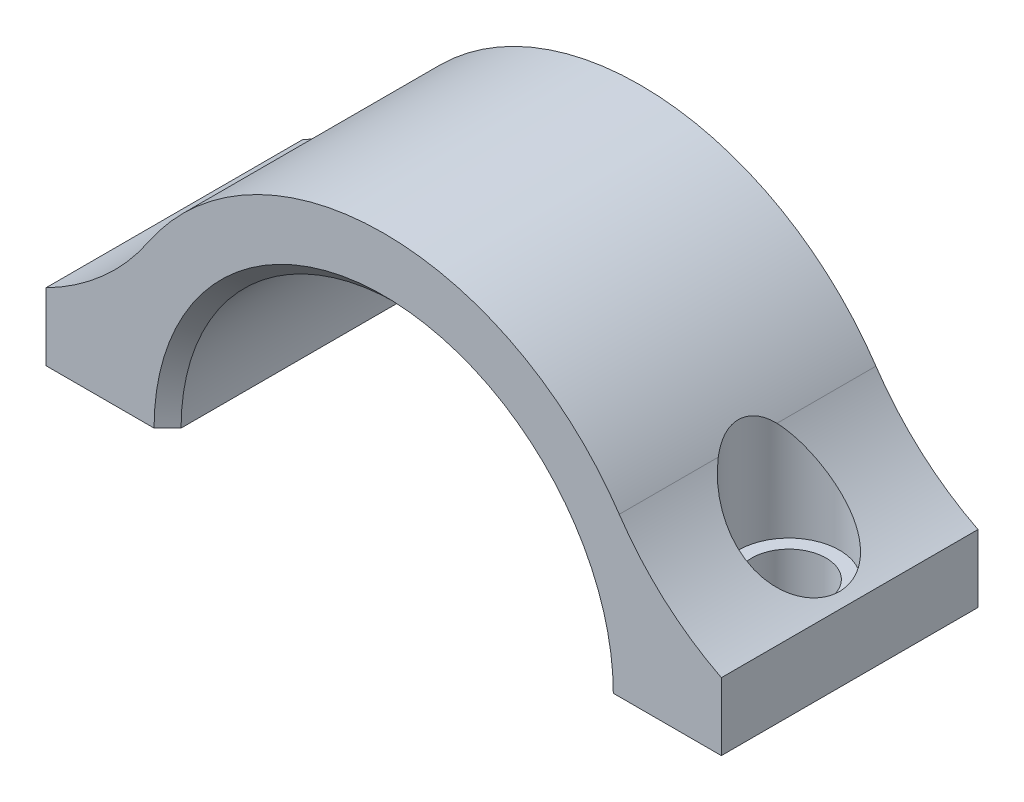
SolidWorks part; units mm, degrees
ref_plane "Alzado" through (0, 0, 0) normal (0, 0, 1) x (1, 0, 0)
ref_plane "Planta" through (0, 0, 0) normal (0, 1, 0) x (1, 0, 0)
ref_plane "Vista lateral" through (0, 0, 0) normal (1, 0, 0) x (0, 0, -1)
sketch "Croquis1" plane through (0, 0, 0) normal (0, 0, 1) x (1, 0, 0)
  line L0 (32, 0) -> (50, 0)
  line L1 (-32, 0) -> (-50, 0)
  line L2 (-50, 0) -> (-50, 10)
  line L3 (-50, 10) -> (-40.7922, 10)
  line L4 (50, 0) -> (50, 10)
  line L5 (50, 10) -> (40.7922, 10)
  arc A0 (32, 0) -> (-32, 0) centre (0, 0) ccw
  arc A1 (40.7922, 10) -> (-40.7922, 10) centre (0, 0) ccw
  dimension "D1" = 64
  dimension "D3" = 10
  dimension "D2" = 18
  dimension "D4" = 18
  dimension "D5" = 10
  dimension "D6" = 10
extrude "Saliente-Extruir1" add sketch "Croquis1" along normal blind 38
ref_plane "Plano1" through (0, 10, 0) normal (0, 1, 0) x (1, 0, 0)
sketch "Croquis2" plane through (0, 10, 0) normal (0, 1, 0) x (1, 0, 0)
  line L0 (32, -38) -> (50, -38) construction
  line L1 (32, -38) -> (50, -38) construction
  line L2 (32, -38) -> (50, 0) construction
  circle A0 centre (41, -19) radius 7.5
  point P2 (41, -19)
  dimension "D1" = 15
extrude "Cortar-Extruir1" cut sketch "Croquis2" along normal blind 36
mirror "Simetría1" about plane through (0, 0, 0) normal (1, 0, 0) of "Cortar-Extruir1"
sketch "Croquis3" plane through (0, 10, 0) normal (0, 1, 0) x (1, 0, 0)
  line L0 (-32, -38) -> (-50, 0) construction
  line L2 (-40.7922, -38) -> (-50, -38) construction
  point P3 (-45.4943, -70.1255)
  point P8 (-41, -19)
hole_wizard "Refrentado para perno con cabeza hexagonal (calidades AB) de M21" positions "Croquis3D1" profile "Croquis4" counterbore size "M2" standard "AS"
sketch3d "Croquis3D1"
  point P0 (-41, 10, 19)
  point P3 (41, 10, 19)
sketch "Croquis4" plane through (-41, 10, 19) normal (1, 0, 0) x (0, 0, 1)
  line L0 (0, 0) -> (0, 43.3047)
  line L1 (0, 43.3047) -> (5.5, 40)
  line L2 (5.5, 40) -> (5.5, 1.4)
  line L3 (5.5, 1.4) -> (7.5, 1.4)
  line L4 (7.5, 1.4) -> (7.5, 0)
  line L5 (7.5, 0) -> (0, 0)
  line L10 (0, 43.3047) -> (-5.5, 40) construction
  line L11 (0, -6.35) -> (0, 107.95) construction
  dimension "Diámetro de taladro" = 11
  dimension "Profundidad de taladro" = 40
  dimension "Diámetro de refrentado" = 15
  dimension "Profundidad de refrentado" = 1.4
  dimension "Ángulo de perforador" = 118
fillet "Redondeo1" radius 40 2 edges at (40.7922, 10, 32.2486) (-40.7922, 10, 5.7514)
chamfer "Chaflán1" distance 2 angle 45 2 edges at (0, 32, 0) (0, 32, 38)
